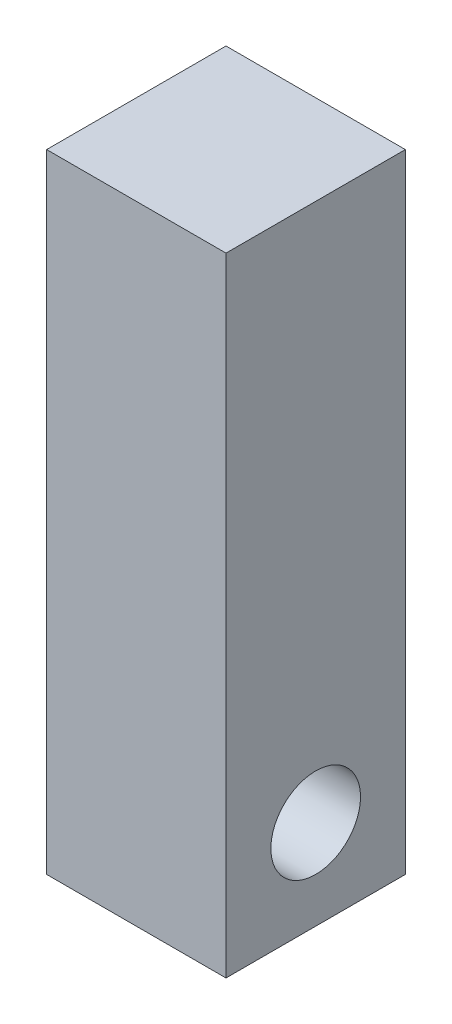
SolidWorks part; units mm, degrees
ref_plane "Front Plane" through (0, 0, 0) normal (0, 0, 1) x (1, 0, 0)
ref_plane "Top Plane" through (0, 0, 0) normal (0, 1, 0) x (1, 0, 0)
ref_plane "Right Plane" through (0, 0, 0) normal (1, 0, 0) x (0, 0, -1)
sketch "Sketch1" plane through (0, 0, 0) normal (0, 1, 0) x (1, 0, 0)
  line L1 (-12.7, 12.7) -> (12.7, 12.7)
  line L2 (-12.7, 12.7) -> (-12.7, -12.7)
  line L3 (-12.7, -12.7) -> (12.7, -12.7)
  line L4 (12.7, 12.7) -> (12.7, -12.7)
  line L5 (-12.7, 12.7) -> (12.7, -12.7) construction
  line L6 (-12.7, -12.7) -> (12.7, 12.7) construction
  point P0 (0, 0)
  dimension "D1" = 25.4
  dimension "D2" = 25.4
extrude "Boss-Extrude1" add sketch "Sketch1" along normal blind 88.9
sketch "Sketch2" plane through (12.7, 0, 0) normal (1, 0, 0) x (0, 0, -1)
  line L0 (-12.7, 0) -> (12.7, 0) construction
  circle A0 centre (0, 12.7) radius 6.35
  point P4 (0, 0)
  dimension "D1" = 12.7
  dimension "D2" = 12.7
extrude "Cut-Extrude1" cut sketch "Sketch2" against normal through all
